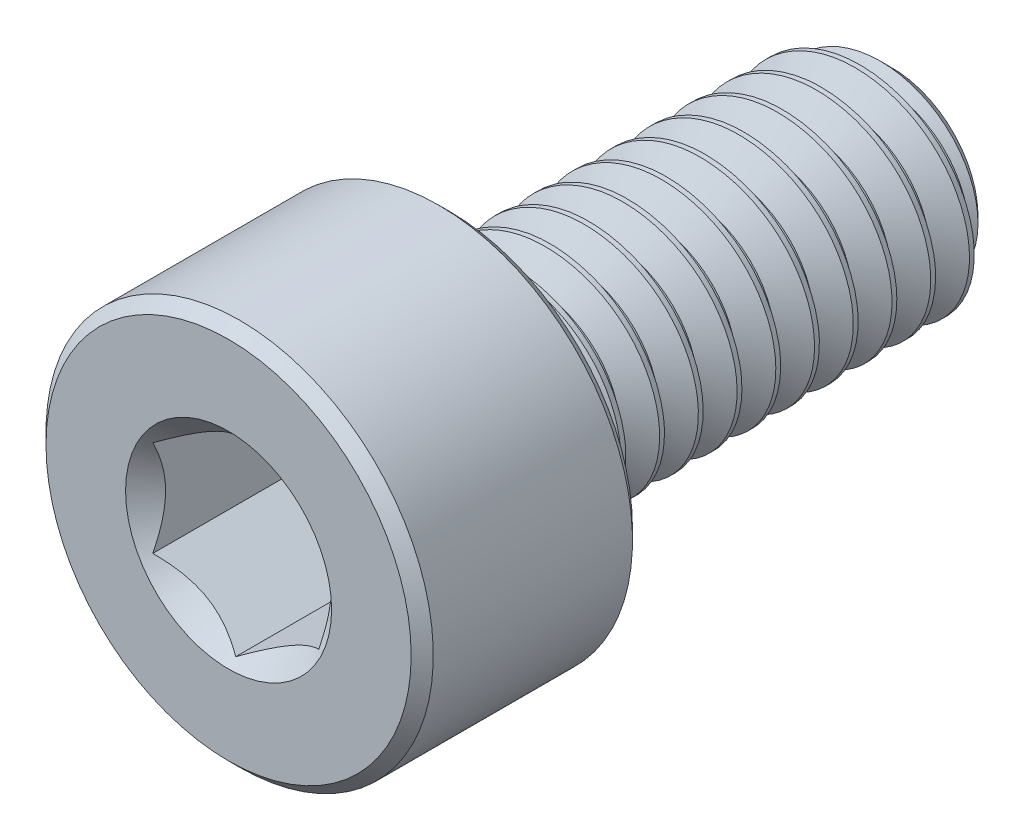
SolidWorks part; units mm, degrees
ref_plane "Front Plane" through (0, 0, 0) normal (0, 0, 1) x (1, 0, 0)
ref_plane "Top Plane" through (0, 0, 0) normal (0, 1, 0) x (1, 0, 0)
ref_plane "Right Plane" through (0, 0, 0) normal (1, 0, 0) x (0, 0, -1)
sketch "Sketch1" plane through (0, 0, 0) normal (1, 0, 0) x (0, 0, -1)
  line L0 (-6, 0) -> (6, 0) construction
  line L1 (6, 0) -> (6, 1.5453) construction
  line L2 (6, 1.5453) -> (5.5453, 2) construction
  line L3 (5.5453, 2) -> (5.475, 2) construction
  line L4 (5.475, 2) -> (-2, 2) construction
  line L5 (-2, 2) -> (-2, 3.5) construction
  line L6 (-2, 3.5) -> (-6, 3.5) construction
  line L7 (-6, 3.5) -> (-6, 0) construction
  line L8 (6, 1.5453) -> (6, 2) construction
  line L9 (5.9563, 2.0758) -> (6.3063, 1.4696) construction
  line L10 (6.3063, 1.4696) -> (6.6563, 2.0758) construction
  line L11 (6.6563, 2.0758) -> (5.9563, 2.0758) construction
  line L12 (6.3063, 2.0758) -> (6.3063, 2) construction
  line L13 (6.3063, 1.4696) -> (6.3063, 1.5453) construction
  line L14 (6.2625, 1.5453) -> (6.35, 1.5453) construction
  line L15 (6, 2) -> (6.6125, 2) construction
  line L16 (5.9781, 2.0379) -> (6.6344, 2.0379) construction
  line L17 (6, 0) -> (6, -2) construction
  line L18 (-2.2, 3.5) -> (-2, 3.3) construction
  line L19 (-5.8, 3.5) -> (-6, 3.3) construction
  line L20 (-2, 2) -> (-2, 0) construction
  line L21 (-2, 1) -> (0.6667, 1) construction
  line L22 (0.6667, 1) -> (3.3333, 1) construction
  line L23 (3.3333, 1) -> (6, 1) construction
  line L24 (0.6667, 1) -> (0.6667, 2) construction
  line L25 (0.6667, 2) -> (0.6667, 3.5) construction
  line L26 (3.3333, 1) -> (3.3333, 3.5) construction
  point P0 (-6, 1.5)
  point P3 (4.25, 2)
  point P4 (0, 0)
  point P18 (3.3333, 2)
  point P22 (6.3063, 1.5453)
  point P24 (5.475, 2)
  point P25 (6.3063, 2)
  point P28 (6.3063, 2.0379)
  point P29 (4.25, -2)
  point P30 (0.6667, 2)
  point P31 (-4, 3.5)
  point P37 (-2.7, 3.5)
  point P38 (-5.7, 3.5)
  point P45 (0.6667, 1)
  point P46 (3.3333, 1)
  dimension "D2" = 0.0875
  dimension "D7" = 0.2
  dimension "D8" = 0.2
  dimension "D9" = 0.2
  dimension "D10" = 0.1
  dimension "D11" = 0.5
  dimension "Drive Size" = 3
  dimension "Head Diameter" = 7
  dimension "Head Height" = 4
  dimension "Thread Pitch" = 0.7
  dimension "Thread Dia" = 4
  dimension "Length" = 8
  dimension "D12" = 0.525
  dimension "D4" = 1.75
  dimension "D3" = 45
sketch "Sketch2" plane through (0, 0, 0) normal (1, 0, 0) x (0, 0, -1)
  line L0 (-6, 0) -> (-6, 3.3)
  line L1 (-5.8, 3.5) -> (-2.2, 3.5)
  line L2 (-2, 3.3) -> (-2, 2.2)
  line L4 (5.5453, 2) -> (6, 1.5453)
  line L5 (6, 1.5453) -> (6, 0)
  line L6 (-2, 3.5) -> (-6, 3.5) construction
  line L7 (6, 0) -> (-6, 0)
  line L8 (-5.8, 3.5) -> (-6, 3.3) construction
  line L10 (-5.8, 3.5) -> (-6, 3.3)
  line L14 (-2.2, 3.5) -> (-2, 3.3) construction
  line L16 (-2.2, 3.5) -> (-2, 3.3)
  line L17 (-2, 2) -> (-2, 3.5) construction
  line L19 (-1.8, 2) -> (5.5453, 2)
  line L20 (5.475, 2) -> (-2, 2) construction
  arc A1 (-2, 2.2) -> (-1.8, 2) centre (-1.8, 2.2) ccw
  dimension "D3" = 0.2
revolve "Revolve1" add sketch "Sketch2" angle 360 about L7
sketch "Sketch3" plane through (0, 0, 6) normal (0, 0, 1) x (1, 0, 0)
  line L1 (1.5, -0.866) -> (1.5, 0.866)
  line L2 (1.5, 0.866) -> (0, 1.7321)
  line L3 (0, 1.7321) -> (-1.5, 0.866)
  line L4 (-1.5, 0.866) -> (-1.5, -0.866)
  line L5 (-1.5, -0.866) -> (0, -1.7321)
  line L6 (0, -1.7321) -> (1.5, -0.866)
  circle A0 centre (0, 0) radius 1.5 construction
  circle A1 centre (0, 0) radius 3.5 construction
  circle A2 centre (0, 0) radius 3.5 construction
  circle A3 centre (0, 0) radius 1.7321 construction
  point P13 (0, 0)
  dimension "D1" = 3.4641
extrude "Cut-Extrude1" cut sketch "Sketch3" against normal offset from surface (3 mm away) 1 up to face at (0, 3.3, 2)
sketch "Sketch4" plane through (0, 0, 6) normal (0, 0, 1) x (1, 0, 0)
  circle A0 centre (0, 0) radius 1.862
  dimension "D1" = 3.7239
extrude "Cut-Extrude2" cut sketch "Sketch4" against normal up to vertex (2 mm away) draft 45 up to point (0, 3.5, 4)
sketch "Sketch11" plane through (0, 0, 0) normal (1, 0, 0) x (0, 0, -1)
  line L0 (-6, 0) -> (6, 0) construction
  line L1 (-6, 0) -> (6, 0) construction
  line L2 (-0.5, 0) -> (-0.5, 2) construction
  line L3 (5.475, 2) -> (-2, 2) construction
  line L4 (4.5, 0) -> (4.5, 2) construction
  line L6 (6, 1.5453) -> (6, 2) construction
  point P2 (-0.5, 0)
  point P3 (4.5, 0)
  dimension "D1" = 1.5
  dimension "D2" = 1.5
sketch "Sketch6" plane through (0, 0, -6) normal (0, 0, -1) x (-1, 0, 0)
  circle A0 centre (0, 0) radius 2
curve "Helix/Spiral1" pitch 0.7 height 8.7 radius 2 centre (0, 0, -6) axis (0, 0, 1) start towards (0, 1, 0)
sketch "Sketch10" plane through (0, 0, 0) normal (1, 0, 0) x (0, 0, -1)
  line L0 (-1.8, -3.5) -> (-1.8, 3.5)
  line L5 (-6, 0) -> (6, 0) construction
  line L6 (-1.8, 2) -> (-1.8, -2) construction
  point P3 (-1.8, 0)
split "Split1" trim tools "Sketch10" bodies to split 106 resulting bodies 114 115
sketch "Sketch7" plane through (0, 0, 0) normal (1, 0, 0) x (0, 0, -1)
  line L0 (5.9781, 2.0379) -> (6.6344, 2.0379)
  line L1 (6.6344, 2.0379) -> (6.35, 1.5453)
  line L2 (6.35, 1.5453) -> (6.2625, 1.5453)
  line L3 (6.2625, 1.5453) -> (5.9781, 2.0379)
sweep "Cut-Sweep1" cut profiles "Sketch7" path "Helix/Spiral1" align with end faces yes
sketch "Sketch8" plane through (0, 0, 0) normal (1, 0, 0) x (0, 0, -1)
  line L0 (-2, 0) -> (-2, 2)
  line L1 (-1.8, -2) -> (-1.8, 2) construction
  line L2 (-2, 2) -> (-1.8, 2)
  line L4 (-1.8, 2) -> (-0.6453, 0)
  line L5 (-0.6453, 0) -> (-2, 0)
  line L6 (5.475, 2) -> (-2, 2) construction
  line L7 (-6, 0) -> (6, 0) construction
  dimension "D1" = 60
revolve "Revolve2" add sketch "Sketch8" angle 360 about L5
equation "\"D2@Sketch1\" = \"Thread Pitch@Sketch1\" / 8"
equation "\"D4@Helix/Spiral1\" = \"Thread Pitch@Sketch1\""
equation "\"D7@Sketch1\" = \"Head Height@Sketch1\" * .05"
equation "\"D8@Sketch1\"=\"D7@Sketch1\""
equation "\"D9@Sketch1\"=\"D7@Sketch1\""
equation "\"D10@Sketch1\"=\"D7@Sketch1\"/2"
equation "\"D11@Sketch1\"=\"D10@Sketch1\"*5"
equation "\"D4@Sketch1\"=\"Thread Pitch@Sketch1\"*2.5"
equation "\"D12@Sketch1\"=\"Thread Pitch@Sketch1\"*.75"
equation "\"D3@Helix/Spiral1\"=\"Length@Sketch1\"+\"Thread Pitch@Sketch1\""
equation "\"D3@Sketch2\"=\"Thread Dia@Sketch1\"*0.05"
equation "\"D1@Sketch11\"=\"Length@Sketch1\"*0.1875"
equation "\"D2@Sketch11\"=\"D1@Sketch11\""
equation "\"D1@Sketch4\"=\"D1@Sketch3\"*1.075"
